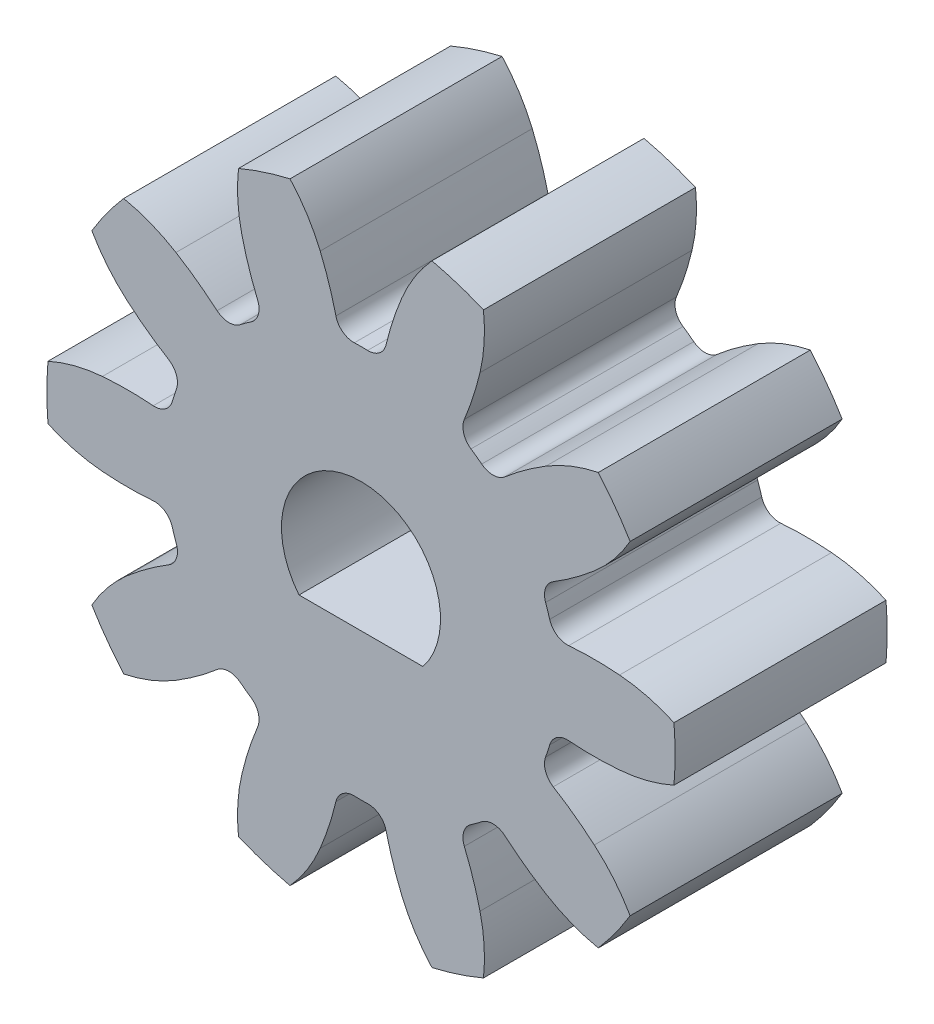
SolidWorks part; units mm, degrees
material "Plain Carbon Steel"
ref_plane "Front" through (0, 0, 0) normal (0, 0, 1) x (1, 0, 0)
ref_plane "Top" through (0, 0, 0) normal (0, 1, 0) x (1, 0, 0)
ref_plane "Right" through (0, 0, 0) normal (1, 0, 0) x (0, 0, -1)
sketch "Sketch1" plane through (0, 0, 0) normal (0, 0, 1) x (1, 0, 0)
  line L0 (0, 0) -> (4.9389, 0) construction
  line L1 (4.9389, 0) -> (5.9267, 0) construction
  circle A0 centre (0, 0) radius 4.9389 construction
  circle A1 centre (0, 0) radius 5.9267
  dimension "pitch_diameter" = 9.8778
  dimension "addendum" = 0.9878
extrude "BLANK DISK" add sketch "Sketch1" along normal mid plane 4
sketch "Sketch2" plane through (0, 0, 2) normal (0, 0, 1) x (1, 0, 0)
  line L0 (0, 0) -> (3.7042, 0) construction
  line L1 (3.7042, 0) -> (4.9389, 0) construction
  line L2 (0, 0) -> (-5.9267, 0) construction
  line L3 (0, 0) -> (-4.7948, -3.4836) construction
  line L4 (-5.0773, -3.0572) -> (-4.4021, -2.2392) construction
  line L5 (-4.4021, -2.2392) -> (-3.386, -1.502) construction
  line L6 (-5.9046, -0.511) -> (-4.8776, -0.7759) construction
  line L7 (-4.8776, -0.7759) -> (-3.6222, -0.7751) construction
  line L8 (-3.946, -2.867) -> (-4.4021, -2.2392) construction
  line L9 (-4.8776, -0.7759) -> (-4.8776, 0) construction
  line L12 (0, 0) -> (-4.8776, -0.7759) construction
  line L13 (0, 0) -> (-4.4021, -2.2392) construction
  line L14 (-4.4021, -2.2392) -> (-2.9167, -5.1593) construction
  line L15 (-4.8776, -0.7759) -> (-5.3922, 2.4595) construction
  line L16 (-4.4021, -2.2392) -> (-4.8776, -0.7759) construction
  line L17 (-3.5229, -1.1447) -> (-3.6222, -0.7751) construction
  line L18 (-3.5229, -1.1447) -> (-3.386, -1.502) construction
  circle A0 centre (0, 0) radius 4.9389 construction
  circle A1 centre (0, 0) radius 3.7042 construction
  circle A2 centre (0, 0) radius 5.9267 construction
  arc A3 (-5.0773, -3.0572) -> (-5.9046, -0.511) centre (0, 0) cw
  arc A4 (-3.386, -1.502) -> (-3.6222, -0.7751) centre (0, 0) cw construction
  arc A6 (-5.0773, -3.0572) -> (-4.4021, -2.2392) centre (-2.3814, -4.5949) cw
  arc A7 (-5.9046, -0.511) -> (-4.8776, -0.7759) centre (-4.6274, 2.3176) ccw
  arc A8 (-4.4021, -2.2392) -> (-3.627, -1.6756) centre (-0.5094, -6.7773) cw
  arc A9 (-4.8776, -0.7759) -> (-3.9192, -0.7763) centre (-4.3957, 5.1836) ccw
  arc A10 (-3.627, -1.6756) -> (-3.4823, -1.2627) centre (-3.8073, -1.3806) ccw
  arc A11 (-3.9192, -0.7763) -> (-3.5594, -1.0253) centre (-3.8917, -1.121) cw
  arc A12 (-3.4823, -1.2627) -> (-3.5594, -1.0253) centre (0, 0) cw
  dimension "D12" = 3.1036
  dimension "D3" = 36
  dimension "D4" = 0.7759
  dimension "D5" = 0.7759
  dimension "D11" = 1.5387
  dimension "D14" = 9
  dimension "D15" = 9
  dimension "base_fillet" = 0.3457
  dimension "pitch_diameter" = 9.8778
  dimension "deddendum" = 1.2347
extrude "GEAR TOOTH CUT" cut sketch "Sketch2" against normal through all
ref_axis "CENTER AXIS" through (0, 0, 50) along (0, 0, -1)
pattern_circular "GEAR TEETH REVOLVE" count 10 over 360 about axis through (0, 0, 50) along (0, 0, -1) of "GEAR TOOTH CUT"
sketch "Sketch4" plane through (0, 0, 2) normal (0, 0, 1) x (1, 0, 0)
  circle A0 centre (0, 0) radius 0.75
  dimension "D1" = 1.5
extrude "Hub Extrude" add sketch "Sketch4" along normal blind 0.635
sketch "Sketch3" plane through (0, 0, 2) normal (0, 0, 1) x (1, 0, 0)
  line L0 (-1.1689, -0.94) -> (1.1689, -0.94)
  arc A0 (1.1689, -0.94) -> (-1.1689, -0.94) centre (0, 0) ccw
  dimension "D1" = 3
  dimension "D2" = 0.94
extrude "HEX BORE CUT" cut sketch "Sketch3" against normal through all and the other way through all
equation "\"N_teeth\" = 10.000000"
equation "\"pitch_diameter\" = 140 / 360"
equation "\"Pd\"=\"N_teeth\"/\"pitch_diameter\""
equation "\"addendum\"=1.000/\"Pd\""
equation "\"face_width\"= 4mm"
equation "\"deddendum\"=1.250/\"Pd\""
equation "\"D3@Sketch2\" = 360/\"N_teeth\""
equation "\"tooth_thickness\"=1.571/\"Pd\""
equation "\"D4@Sketch2\" = \"tooth_thickness\"/2"
equation "\"D5@Sketch2\" = \"tooth_thickness\"/2"
equation "\"Pressure_Angle\"=14.500000"
equation "\"base_fillet\"=0.35/\"Pd\""
equation "\"D12@Sketch2\" = 2*\"tooth_thickness\""
equation "\"hub_diameter\"= 1.5mm"
equation "\"bore\"= 0.125000"
equation "\"hub_projection\"=0.250000"
equation "\"sss_diam\"=0.062500"
